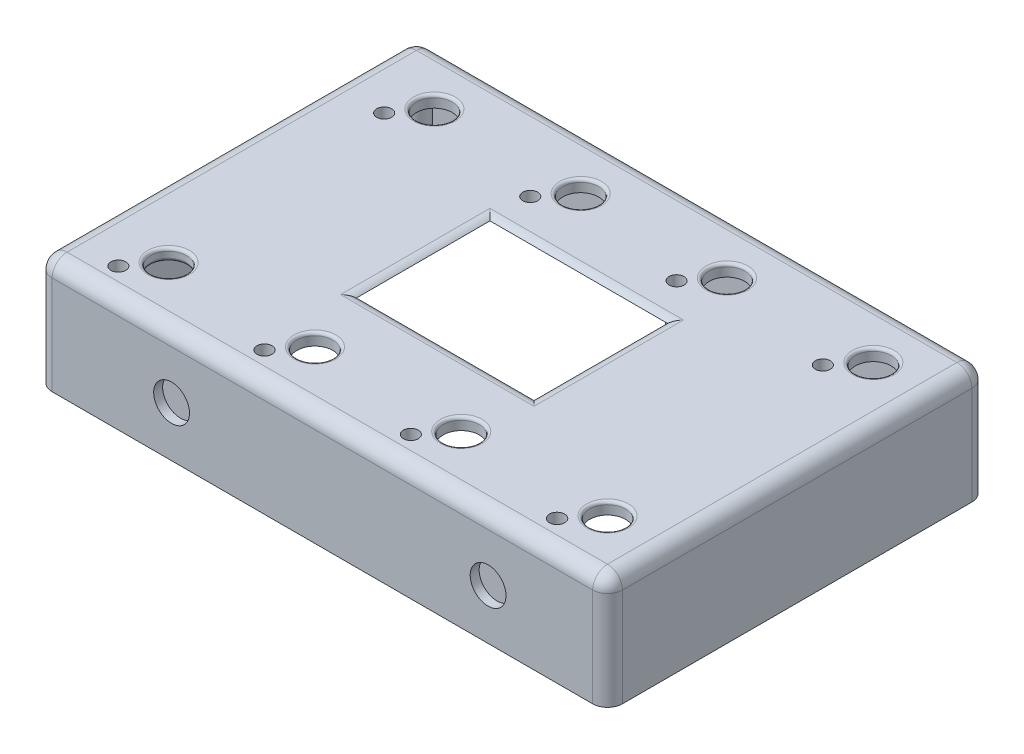
SolidWorks part; units mm, degrees
ref_plane "Front Plane" through (0, 0, 0) normal (0, 0, 1) x (1, 0, 0)
ref_plane "Top Plane" through (0, 0, 0) normal (0, 1, 0) x (1, 0, 0)
ref_plane "Right Plane" through (0, 0, 0) normal (1, 0, 0) x (0, 0, -1)
sketch "Sketch3" plane through (0, 0, 0) normal (0, 1, 0) x (1, 0, 0)
sketch "Sketch11" plane through (0, 0, 0) normal (0, 1, 0) x (1, 0, 0)
  line L1 (-91.5, 59.5) -> (91.5, 59.5)
  line L2 (-91.5, 59.5) -> (-91.5, -59.5)
  line L3 (-91.5, -59.5) -> (91.5, -59.5)
  line L4 (91.5, 59.5) -> (91.5, -59.5)
  line L5 (-91.5, 59.5) -> (91.5, -59.5) construction
  line L6 (-91.5, -59.5) -> (91.5, 59.5) construction
  point P0 (0, 0)
  dimension "D1" = 183
  dimension "D2" = 119
extrude "Boss-Extrude2" add sketch "Sketch11" along normal blind 34
shell "Shell19" thickness 4 removed face at (0, 0, 0) outward yes
sketch "Sketch12" plane through (0, 0, 0) normal (0, -1, 0) x (-1, 0, 0)
  circle A0 centre (-89.2941, 57.1284) radius 4
  circle A1 centre (89.3018, 57.1284) radius 4
  circle A2 centre (89.3018, -56.8526) radius 4
  circle A4 centre (-89.2941, -56.8526) radius 4
  circle A5 centre (0, -56.8526) radius 4
  circle A6 centre (0, 57.1284) radius 4
  point P4 (90.7579, 58.6667)
  point P7 (90.7579, -56.0823)
  point P8 (90.7579, -58.7963)
  point P9 (0, 0)
  point P10 (89.3018, -56.8526)
  point P11 (0, 0)
  point P12 (0, 0)
  point P15 (-90.716, -58.7963)
  point P16 (89.3018, 57.1284)
  point P17 (0, 0)
  point P18 (-89.2941, 57.1284)
  point P19 (-89.2941, -56.8526)
  point P22 (0, -56.8526)
  point P25 (0, 57.1284)
extrude "Boss-Extrude4" add sketch "Sketch12" against normal blind 34
hole_wizard "#6-32 Tapped Hole1" positions "Sketch13" profile "Sketch14" tap size "#6-32" standard "ANSI Inch"
sketch "Sketch13" plane through (0, 0, 0) normal (0, -1, 0) x (-1, 0, 0)
  point P0 (-89.2941, 57.1284)
  point P3 (-89.2941, -56.8526)
  point P6 (0, -56.8526)
  point P8 (0, 57.1284)
  point P11 (89.3018, 57.1284)
  point P14 (89.3018, -56.8526)
sketch "Sketch14" plane through (89.2941, 0, -57.1284) normal (1, 0, 0) x (0, 0, -1)
  line L0 (0, 0) -> (0, 11.7827)
  line L1 (0, 11.7827) -> (1.3525, 10.97)
  line L2 (1.3525, 10.97) -> (1.3525, 0.8685)
  line L3 (1.3525, 0.8685) -> (2.3876, 0)
  line L5 (2.3876, 0) -> (0, 0)
  line L6 (-1.3525, 0.8685) -> (-2.3876, 0) construction
  line L10 (0, 11.7827) -> (-1.3526, 10.97) construction
  line L11 (0, -6.35) -> (0, 107.95) construction
  dimension "Tap Drill Dia." = 2.7051
  dimension "Tap Drill Depth" = 10.97
  dimension "Near C'Sink Dia." = 4.7752
  dimension "Near C'Sink Angle" = 100
  dimension "Drill Angle" = 118
cosmetic thread "Hole Thread1" parameters "D1"=7.01, "D2"=3.5052
cosmetic thread "Hole Thread2" parameters "D1"=7.01, "D2"=3.5052
cosmetic thread "Hole Thread3" parameters "D1"=7.01, "D2"=3.5052
cosmetic thread "Hole Thread4" parameters "D1"=7.01, "D2"=3.5052
cosmetic thread "Hole Thread5" parameters "D1"=7.01, "D2"=3.5052
cosmetic thread "Hole Thread6" parameters "D1"=7.01, "D2"=3.5052
fillet "Fillet1" radius 5 8 edges at (-95.5, 19, 63.5) (-95.5, 19, -63.5) (95.5, 19, -63.5) (-95.5, 38, 0) (0, 38, 63.5) (95.5, 38, 0) (0, 38, -63.5) (95.5, 19, 63.5)
sketch "Sketch15" plane through (0, 0, 0) normal (0, 1, 0) x (1, 0, 0)
  line L0 (90.5, 58.5) -> (-90.5, 58.5) construction
  line L2 (-90.5, 58.5) -> (-90.5, -58.5) construction
  circle A0 centre (-70.5, 44.5) radius 6
  dimension "D1" = 14
  dimension "D2" = 20
extrude "Cut-Extrude2" cut sketch "Sketch15" along normal blind 153
fillet "Fillet2" radius 1 1 edges at (-70.5, 38, -38.5)
sketch "Sketch16" plane through (0, 38, 0) normal (0, 1, 0) x (1, 0, 0)
  line L0 (90.5, -58.5) -> (90.5, 58.5) construction
  line L2 (90.5, 58.5) -> (-90.5, 58.5) construction
  line L3 (-90.5, 58.5) -> (-90.5, -58.5) construction
  line L4 (-90.5, -58.5) -> (90.5, -58.5) construction
  line L6 (-29.75, 22.375) -> (29.75, 22.375)
  line L7 (-29.75, 22.375) -> (-29.75, -22.375)
  line L8 (-29.75, -22.375) -> (29.75, -22.375)
  line L9 (29.75, 22.375) -> (29.75, -22.375)
  line L10 (-29.75, 22.375) -> (29.75, -22.375) construction
  line L11 (-29.75, -22.375) -> (29.75, 22.375) construction
  circle A0 centre (76.5, 44.5) radius 6
  circle A1 centre (-21.5, 44.5) radius 6
  circle A2 centre (27.5, 44.5) radius 6
  circle A4 centre (-70.5, -44.5) radius 6
  circle A5 centre (76.5, -44.5) radius 6
  circle A6 centre (27.5, -44.5) radius 6
  circle A7 centre (-21.5, -44.5) radius 6
  point P0 (0, 0)
  point P3 (-25.1667, 43.5197)
  point P12 (-19.1418, -43.5)
  point P30 (0, 0)
  point P31 (-25.1667, -44.5)
  point P32 (26.7573, -44.5)
  point P33 (28.4039, -44.5)
  point P34 (-27.169, -44.5)
  point P35 (-27.169, 43.5197)
  point P36 (28.4039, 44.5)
  point P37 (0, 0)
  dimension "D11" = 14
  dimension "D2" = 14
  dimension "D3" = 14
  dimension "D4" = 14
  dimension "D5" = 14
  dimension "D6" = 14
  dimension "D7" = 20
  dimension "D8" = 14
  dimension "D9" = 44.75
  dimension "D10" = 59.5
  dimension "D12" = 14
  dimension "D13" = 14
  dimension "D14" = 147
  dimension "D15" = 49
  dimension "D16" = 49
  dimension "D17" = 49
  dimension "D18" = 49
  dimension "D19" = 49
extrude "Cut-Extrude3" cut sketch "Sketch16" against normal blind 153
fillet "Fillet3" radius 1 1 edges at (-21.5, 38, -38.5)
fillet "Fillet4" radius 1 1 edges at (27.5, 38, -38.5)
fillet "Fillet5" radius 1 1 edges at (76.5, 38, -38.5)
fillet "Fillet6" radius 1 1 edges at (-70.5, 34, 50.5)
fillet "Fillet7" radius 1 1 edges at (-70.5, 38, 50.5)
fillet "Fillet8" radius 1 1 edges at (-21.5, 38, 50.5)
fillet "Fillet9" radius 1 1 edges at (27.5, 38, 50.5)
fillet "Fillet10" radius 1 1 edges at (76.5, 38, 50.5)
sketch "Sketch17" plane through (0, 0, 63.5) normal (0, 0, 1) x (1, 0, 0)
  line L0 (-90.5, 33) -> (-90.5, 0) construction
  line L1 (95.5, 33) -> (95.5, 0) construction
  circle A0 centre (-50.5, 16.8239) radius 6
  circle A1 centre (55.5, 16.8239) radius 6
  point P0 (-51.3249, 16.8239)
  dimension "D1" = 40
  dimension "D2" = 40
sketch "Sketch19" plane through (0, 0, 0) normal (1, 0, 0) x (0, 0, -1)
  line L1 (5.2671, 25.9206) -> (19.2671, 25.9206)
  line L2 (5.2671, 25.9206) -> (5.2671, 17.6706)
  line L3 (5.2671, 17.6706) -> (19.2671, 17.6706)
  line L4 (19.2671, 25.9206) -> (19.2671, 17.6706)
  line L5 (5.2671, 25.9206) -> (19.2671, 17.6706) construction
  line L6 (5.2671, 17.6706) -> (19.2671, 25.9206) construction
  circle A1 centre (-37.2354, 21.7956) radius 4
  circle A3 centre (27.8443, 21.7956) radius 4
  point P0 (12.2671, 21.7956)
  point P9 (8.5359, 21.7956)
  point P10 (27.8443, 21.7956)
  point P11 (13.69, 21.7956)
  point P12 (12.2671, 21.7956)
  point P13 (-37.2354, 21.7956)
  dimension "D1" = 14
  dimension "D2" = 8.25
extrude "Cut-Extrude4" cut sketch "Sketch19" against normal blind 153
extrude "Cut-Extrude5" cut sketch "Sketch17" against normal blind 3
sketch "Sketch22" plane through (0, 34, 0) normal (0, -1, 0) x (-1, 0, 0)
  line L0 (29.75, -22.375) -> (-29.75, -22.375) construction
  line L1 (37.25, -24.725) -> (-32.35, -24.725)
  line L2 (37.25, -24.725) -> (37.25, 25.475)
  line L3 (37.25, 25.475) -> (-32.35, 25.475)
  line L4 (-32.35, -24.725) -> (-32.35, 25.475)
  line L7 (29.75, 22.375) -> (29.75, -22.375) construction
  dimension "D1" = 50.2
  dimension "D2" = 69.6
  dimension "D3" = 2.35
  dimension "D4" = 7.5
extrude "Cut-Extrude6" cut sketch "Sketch22" against normal blind 3
sketch "Sketch23" plane through (0, 34, 0) normal (0, -1, 0) x (-1, 0, 0)
  circle A0 centre (77.8708, -53.9695) radius 2.5
  circle A1 centre (70.5, -44.5) radius 7 construction
  circle A2 centre (29.0598, -53.8193) radius 2.5
  circle A3 centre (-19.9335, -53.8139) radius 2.5
  circle A4 centre (-68.7704, -53.6789) radius 2.5368
  circle A5 centre (77.7539, 34.9407) radius 2.5
  circle A6 centre (29.087, 35.2028) radius 2.5
  circle A7 centre (-19.8724, 35.2361) radius 2.5
  circle A8 centre (-68.783, 35.3104) radius 2.5
  circle A9 centre (70.5, 44.5) radius 6 construction
  circle A10 centre (21.5, -44.5) radius 6 construction
  circle A11 centre (-27.5, -44.5) radius 6 construction
  circle A12 centre (-76.5, -44.5) radius 6 construction
  circle A13 centre (21.5, 44.5) radius 6 construction
  circle A14 centre (-27.5, 44.5) radius 6 construction
  circle A15 centre (-76.5, 44.5) radius 6 construction
  point P0 (29.0598, 34.9407)
  dimension "D1" = 12
  dimension "D2" = 12
  dimension "D3" = 12
  dimension "D4" = 12
  dimension "D5" = 12
  dimension "D6" = 12
  dimension "D7" = 12
  dimension "D8" = 12
extrude "Cut-Extrude7" cut sketch "Sketch23" against normal blind 12
fillet "Fillet17" radius 4 4 edges at (0, 38, 22.375) (0, 38, -22.375) (-29.75, 38, 0) (29.75, 38, 0)
